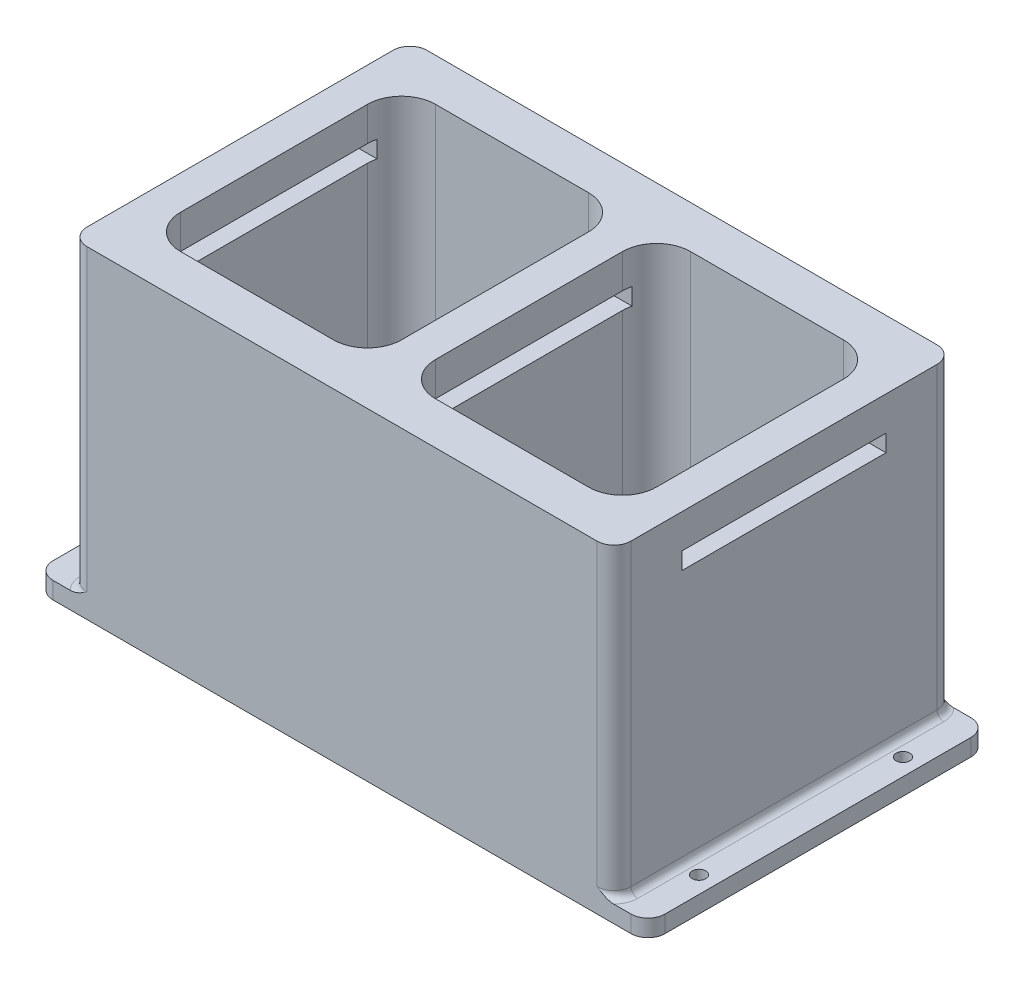
SolidWorks part; units mm, degrees
material "ABS"
ref_plane "Front Plane" through (0, 0, 0) normal (0, 0, 1) x (1, 0, 0)
ref_plane "Top Plane" through (0, 0, 0) normal (0, 1, 0) x (1, 0, 0)
ref_plane "Right Plane" through (0, 0, 0) normal (1, 0, 0) x (0, 0, -1)
sketch "Sketch1" plane through (0, 0, 0) normal (0, 1, 0) x (1, 0, 0)
  line L1 (90, -50) -> (-90, -50)
  line L2 (90, -50) -> (90, 50)
  line L3 (90, 50) -> (-90, 50)
  line L4 (-90, -50) -> (-90, 50)
  line L5 (90, -50) -> (-90, 50) construction
  line L6 (90, 50) -> (-90, -50) construction
  point P0 (0, 0)
  dimension "D1" = 180
  dimension "D2" = 100
extrude "Boss-Extrude1" add sketch "Sketch1" along normal blind 5
sketch "Sketch2" plane through (0, 5, 0) normal (0, 1, 0) x (1, 0, 0)
  line L0 (90, 50) -> (-90, 50) construction
  line L1 (80, -50) -> (-80, -50)
  line L2 (80, -50) -> (80, 50)
  line L3 (80, 50) -> (-80, 50)
  line L4 (-80, -50) -> (-80, 50)
  line L5 (80, -50) -> (-80, 50) construction
  line L6 (80, 50) -> (-80, -50) construction
  line L7 (-90, 50) -> (-90, -50) construction
  line L9 (-80, 0) -> (-90, 0) construction
  point P0 (0, 0)
  dimension "D1" = 10
extrude "Boss-Extrude2" add sketch "Sketch2" along normal blind 90
sketch "Sketch3" plane through (0, 5, 0) normal (0, 1, 0) x (1, 0, 0)
  line L0 (-85, 50) -> (-85, 30) construction
  line L1 (-80, 50) -> (-90, 50) construction
  line L3 (0, -2.75) -> (0, 2.75) construction
  line L4 (-2.75, 0) -> (2.75, 0) construction
  circle A0 centre (-85, 30) radius 2
  circle A1 centre (85, 30) radius 2
  circle A2 centre (85, -30) radius 2
  circle A3 centre (-85, -30) radius 2
  dimension "D2" = 4
  dimension "D1" = 20
extrude "Cut-Extrude1" cut sketch "Sketch3" against normal through all
fillet "Fillet1" radius 5 8 edges at (-90, 2.5, -50) (-80, 50, -50) (90, 2.5, -50) (80, 50, -50) (-90, 2.5, 50) (-80, 50, 50) (90, 2.5, 50) (80, 50, 50)
fillet "Fillet2" radius 2 6 edges at (78.5355, 5, 48.5355) (78.5355, 5, -48.5355) (-78.5355, 5, -48.5355) (-78.5355, 5, 48.5355) (80, 5, 0) (-80, 5, 0)
sketch "Sketch4" plane through (0, 95, 0) normal (0, 1, 0) x (1, 0, 0)
  line L0 (-70, 0) -> (-80, 0) construction
  line L1 (-5, -37.5) -> (-70, -37.5)
  line L2 (-5, -37.5) -> (-5, 37.5)
  line L3 (-5, 37.5) -> (-70, 37.5)
  line L4 (-70, -37.5) -> (-70, 37.5)
  line L5 (-5, -37.5) -> (-70, 37.5) construction
  line L6 (-5, 37.5) -> (-70, -37.5) construction
  line L7 (-80, 45) -> (-80, -45) construction
  line L8 (-5, 0) -> (5, 0) construction
  line L9 (0, -52.25) -> (0, 52.25) construction
  line L10 (5, 37.5) -> (70, 37.5)
  line L11 (70, -37.5) -> (70, 37.5)
  line L12 (5, -37.5) -> (70, -37.5)
  line L13 (5, -37.5) -> (5, 37.5)
  point P0 (-37.5, 0)
  dimension "D1" = 65
  dimension "D2" = 75
extrude "Cut-Extrude2" cut sketch "Sketch4" against normal blind 85
fillet "Fillet3" radius 10 8 edges at (70, 52.5, 37.5) (5, 52.5, 37.5) (70, 52.5, -37.5) (5, 52.5, -37.5) (-70, 52.5, 37.5) (-5, 52.5, 37.5) (-5, 52.5, -37.5) (-70, 52.5, -37.5)
sketch "Sketch5" plane through (-80, 0, 0) normal (-1, 0, 0) x (0, 0, 1)
  line L0 (-45, 82.5) -> (-30, 82.5) construction
  line L1 (-30, 85) -> (30, 85)
  line L2 (-30, 85) -> (-30, 80)
  line L3 (-30, 80) -> (30, 80)
  line L4 (30, 85) -> (30, 80)
  line L5 (-45, 95) -> (-45, 7) construction
  line L6 (30, 82.5) -> (45, 82.5) construction
  line L7 (45, 7) -> (45, 95) construction
  line L8 (-45, 95) -> (45, 95) construction
  dimension "D1" = 60
  dimension "D2" = 10
  dimension "D3" = 5
extrude "Cut-Extrude3" cut sketch "Sketch5" against normal through all both and the other way through all
